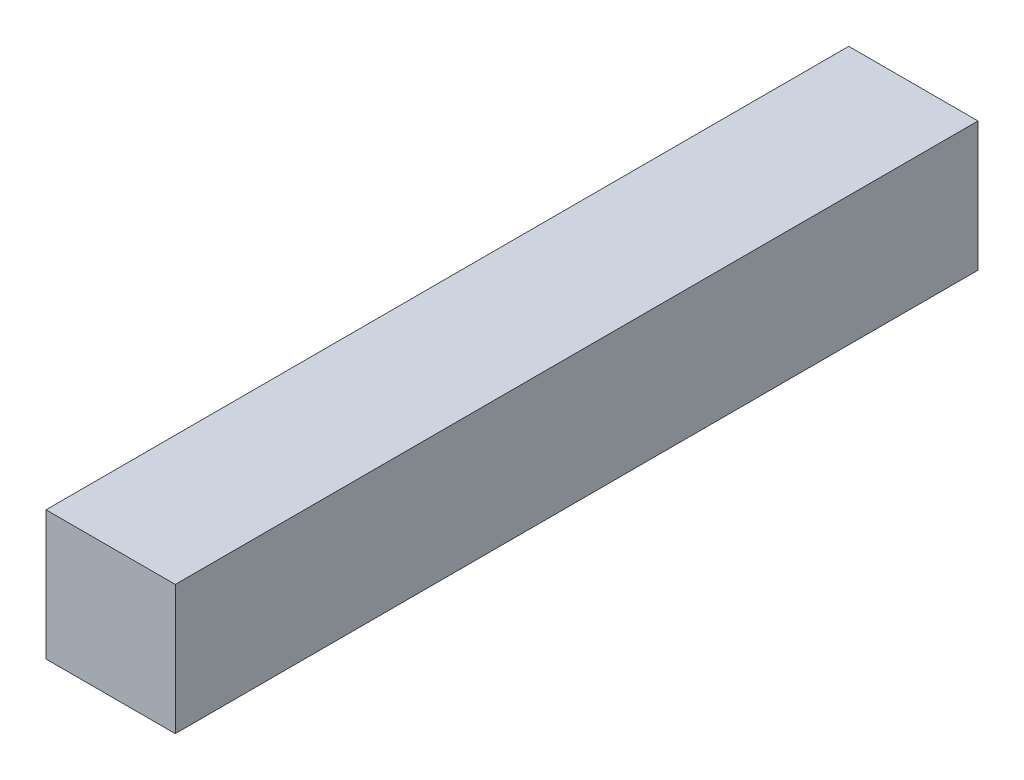
SolidWorks part; units mm, degrees
ref_plane "Front Plane" through (0, 0, 0) normal (0, 0, 1) x (1, 0, 0)
ref_plane "Top Plane" through (0, 0, 0) normal (0, 1, 0) x (1, 0, 0)
ref_plane "Right Plane" through (0, 0, 0) normal (1, 0, 0) x (0, 0, -1)
sketch "Sketch1" plane through (0, 0, 0) normal (0, 0, 1) x (1, 0, 0)
  line L1 (-12.7, -12.7) -> (12.7, -12.7)
  line L2 (-12.7, -12.7) -> (-12.7, 12.7)
  line L3 (-12.7, 12.7) -> (12.7, 12.7)
  line L4 (12.7, -12.7) -> (12.7, 12.7)
  line L5 (-12.7, -12.7) -> (12.7, 12.7) construction
  line L6 (-12.7, 12.7) -> (12.7, -12.7) construction
  point P0 (0, 0)
  dimension "D1" = 25.4
  dimension "D2" = 25.4
extrude "Boss-Extrude1" add sketch "Sketch1" along normal mid plane 157.734
